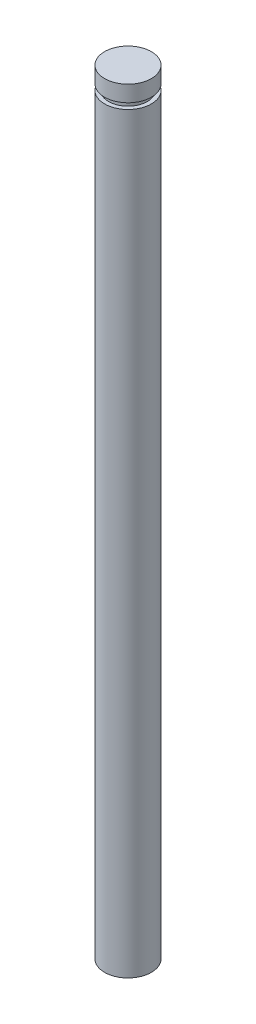
SolidWorks part; units mm, degrees
ref_plane "Front Plane" through (0, 0, 0) normal (0, 0, 1) x (1, 0, 0)
ref_plane "Top Plane" through (0, 0, 0) normal (0, 1, 0) x (1, 0, 0)
ref_plane "Right Plane" through (0, 0, 0) normal (1, 0, 0) x (0, 0, -1)
sketch "Sketch1" plane through (0, 0, 0) normal (0, 1, 0) x (1, 0, 0)
  circle A0 centre (0, 0) radius 0.725
  dimension "D1" = 1.45
extrude "Boss-Extrude1" add sketch "Sketch1" along normal blind 24
sketch "Sketch2" plane through (0, 24, 0) normal (0, 1, 0) x (1, 0, 0)
  circle A0 centre (0, 0) radius 0.725
  circle A1 centre (0, 0) radius 0.6
  dimension "D1" = 1.45
  dimension "D2" = 1.2
extrude "Cut-Extrude1" cut sketch "Sketch2" against normal blind 0.68
extrude "Boss-Extrude2" add sketch "Sketch2<2>" against normal blind 0.5
sketch "Sketch2<2>" plane through (0, 24, 0) normal (0, 1, 0) x (1, 0, 0) same geometry as "Sketch2"
